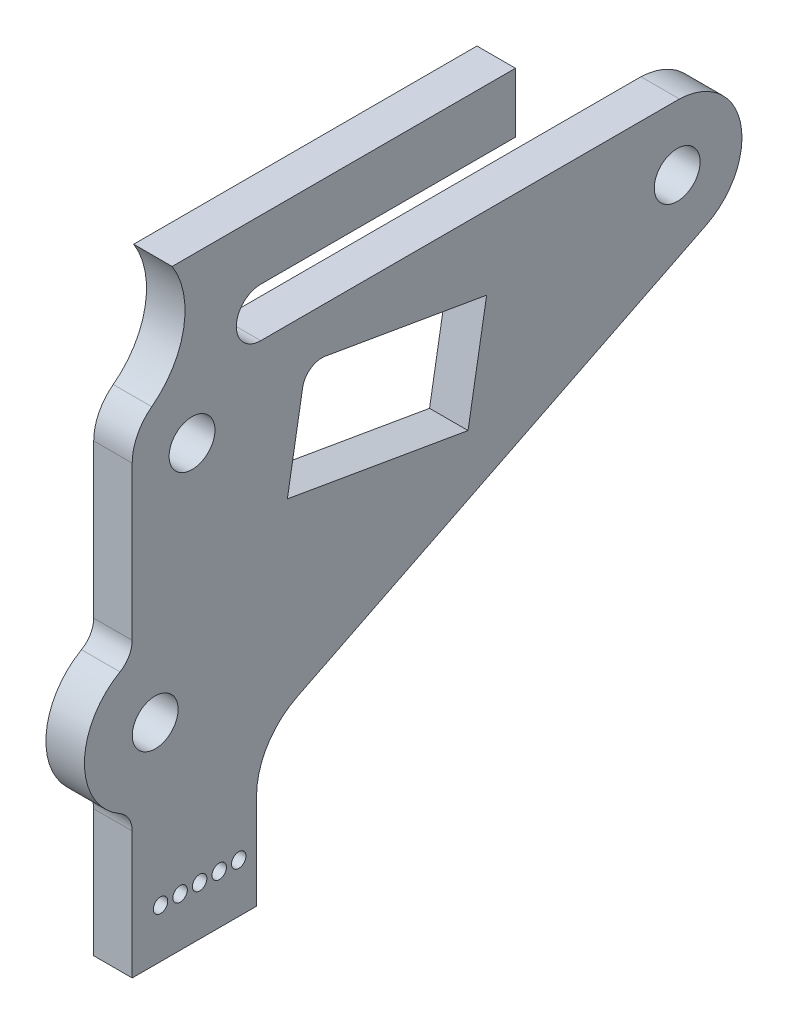
SolidWorks part; units mm, degrees
material "Hardboard"
ref_plane "Front Plane" through (0, 0, 0) normal (0, 0, 1) x (1, 0, 0)
ref_plane "Top Plane" through (0, 0, 0) normal (0, 1, 0) x (1, 0, 0)
ref_plane "Right Plane" through (0, 0, 0) normal (1, 0, 0) x (0, 0, -1)
sketch "Sketch1" plane through (0, 0, 0) normal (1, 0, 0) x (0, 0, -1)
  line L0 (-56.6254, 5.3138) -> (-52.4758, 5.3138) construction
  line L1 (-56.6254, 2.387) -> (-56.6254, -13.5592)
  line L2 (-56.6254, -43.9437) -> (-43.7075, -43.9437)
  line L3 (-43.7075, -43.9437) -> (-43.7075, -34.0304)
  line L4 (-43.7075, -20.39) -> (-25.8088, -20.39) construction
  line L5 (6.73, -20.39) -> (6.73, 6.726) construction
  line L6 (0.2329, 6.726) -> (0, 0) construction
  line L7 (6.73, 0) -> (0, 0) construction
  line L8 (-36.5684, 1.976) -> (-19.7977, -0.9146)
  line L9 (-38.916, 0.3187) -> (-40.5041, -8.8947)
  line L10 (-19.7977, -0.9146) -> (-21.7309, -12.1305)
  line L11 (-40.5041, -8.8947) -> (-21.7309, -12.1305)
  line L12 (-45.5531, -38.8637) -> (-47.5851, -38.8637) construction
  line L13 (-43.2664, 11.806) -> (-16.804, 11.806)
  line L14 (-16.804, 11.806) -> (-16.804, 18.009)
  line L15 (-16.804, 18.009) -> (-52.4758, 18.009)
  line L16 (-52.4758, 18.009) -> (-52.4758, 5.3138) construction
  line L17 (-43.2664, 6.726) -> (0.2329, 6.726)
  line L18 (-42.9558, -7.0581) -> (-43.1648, 5.6402) construction
  line L19 (0.2329, 6.726) -> (6.73, 6.726) construction
  line L20 (-25.8088, -20.39) -> (6.73, -20.39) construction
  line L21 (-25.8088, -20.39) -> (3.0033, -6.0227)
  line L22 (-25.8088, -20.39) -> (-39.488, -27.2112)
  line L23 (-43.7075, -29.3153) -> (-43.7075, -20.39) construction
  line L24 (-56.6254, -15.1828) -> (-56.6254, -29.0916) construction
  line L25 (-56.6254, -30.7152) -> (-56.6254, -43.9437)
  circle A0 centre (0, 0) radius 2.3813
  circle A1 centre (-45.5531, -38.8637) radius 0.75
  circle A2 centre (-47.5851, -38.8637) radius 0.75
  circle A3 centre (-49.6171, -38.8637) radius 0.75
  circle A4 centre (-51.6491, -38.8637) radius 0.75
  circle A5 centre (-54.2362, -22.1372) radius 2.3812
  circle A6 centre (-50.4101, 1.0794) radius 2.3812
  circle A7 centre (-53.6811, -38.8637) radius 0.75
  arc A8 (-43.2664, 6.726) -> (-43.2664, 11.806) centre (-43.2664, 9.266) cw
  arc A9 (-52.4758, 18.009) -> (-54.597, 6.4483) centre (-59.8045, 13.3788) cw
  arc A10 (0.2329, 6.726) -> (3.0033, -6.0227) centre (0, 0) cw
  arc A11 (-43.7075, -34.0304) -> (-39.488, -27.2112) centre (-36.0875, -34.0304) cw
  arc A12 (-56.6254, 2.387) -> (-54.597, 6.4483) centre (-51.5454, 2.387) cw
  arc A13 (-57.8999, -15.7615) -> (-57.8999, -28.5129) centre (-54.2362, -22.1372) ccw
  arc A14 (-56.6254, -13.5592) -> (-57.8999, -15.7615) centre (-59.1654, -13.5592) cw
  arc A15 (-56.6254, -30.7152) -> (-57.8999, -28.5129) centre (-59.1654, -30.7152) ccw
  arc A16 (-38.916, 0.3187) -> (-36.5684, 1.976) centre (-36.9135, -0.0265) cw
  point P61 (-38.5709, 2.3212)
  dimension "D1" = 4.7625
  dimension "D2" = 1.5
  dimension "D9" = 7.62
  dimension "D10" = 5.08
  dimension "D11" = 2.54
  dimension "D12" = 2.54
  dimension "D13" = 2.032
  dimension "D3" = 5.08
  dimension "D5" = 2.032
  dimension "D6" = 19.05
  dimension "D7" = 6.203
  dimension "D8" = 5.08
  dimension "D4" = 5
extrude "Boss-Extrude1" add sketch "Sketch1" along normal mid plane 4
